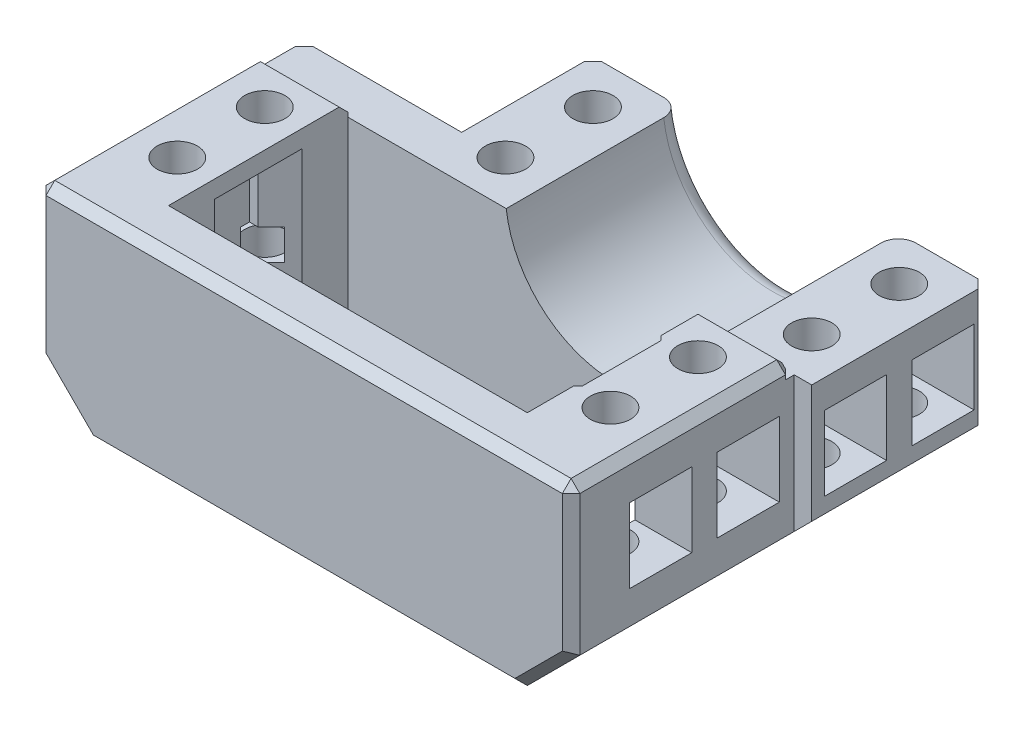
SolidWorks part; units mm, degrees
ref_plane "Front Plane" through (0, 0, 0) normal (0, 0, 1) x (1, 0, 0)
ref_plane "Top Plane" through (0, 0, 0) normal (0, 1, 0) x (1, 0, 0)
ref_plane "Right Plane" through (0, 0, 0) normal (1, 0, 0) x (0, 0, -1)
sketch "Sketch1" plane through (0, 0, 0) normal (0, 1, 0) x (1, 0, 0)
  line L0 (0, -10.25) -> (0, 10.25) construction
  line L1 (-20.5, 0) -> (20.5, 0) construction
  line L2 (-20.5, 10.25) -> (20.5, 10.25)
  line L3 (20.5, 10.25) -> (20.5, -10.25)
  line L4 (20.5, -10.25) -> (-20.5, -10.25)
  line L5 (-20.5, -10.25) -> (-20.5, 10.25)
  line L6 (0, -10.25) -> (0, -15.25) construction
  line L7 (0, -15.25) -> (-30.5, -15.25)
  line L8 (0, -15.25) -> (30.5, -15.25)
  line L9 (-30.5, -15.25) -> (-30.5, 30.25)
  line L10 (-30.5, 30.25) -> (30.5, 30.25)
  line L11 (30.5, 30.25) -> (30.5, -15.25)
  point P4 (0, 0)
  point P8 (0, 0)
  point P11 (0, 10.25)
  dimension "D1" = 41
  dimension "D2" = 20.5
  dimension "D3" = 5
  dimension "D4" = 30.5
  dimension "D5" = 30.5
  dimension "D6" = 45.5
extrude "Boss-Extrude1" add sketch "Sketch1" along normal blind 23
ref_plane "Plane1" through (0, 0, -30.25) normal (0, 0, -1) x (-1, 0, 0)
sketch "Sketch2" plane through (0, 0, -30.25) normal (0, 0, -1) x (-1, 0, 0)
  line L0 (0, 0) -> (0, 23) construction
  line L1 (-30.5, 0) -> (30.5, 0) construction
  line L2 (-30.5, 23) -> (30.5, 23) construction
  line L3 (0, 23) -> (-10, 23) construction
  circle A0 centre (-10, 23) radius 12.5
  dimension "D1" = 25
  dimension "D2" = 10
extrude "Cut-Extrude1" cut sketch "Sketch2" against normal blind 20
ref_plane "Plane2" through (30.5, 0, 0) normal (1, 0, 0) x (0, 0, -1)
sketch "Sketch3" plane through (30.5, 0, 0) normal (1, 0, 0) x (0, 0, -1)
  line L0 (30.25, 23) -> (10.25, 23)
  line L1 (10.25, 23) -> (10.25, 0)
  line L2 (10.25, 0) -> (30.25, 0)
  line L3 (30.25, 0) -> (30.25, 23)
extrude "Boss-Extrude2" add sketch "Sketch3" along normal blind 2
ref_plane "Plane3" through (0, 23, 0) normal (0, 1, 0) x (1, 0, 0)
sketch "Sketch4" plane through (0, 23, 0) normal (0, 1, 0) x (1, 0, 0)
  line L0 (-2.5, 20.25) -> (-7.5, 20.25) construction
  line L1 (-2.5, 10.25) -> (-2.5, 30.25) construction
  line L2 (-7.5, 15.25) -> (-7.5, 25.25) construction
  line L3 (22.5, 20.25) -> (27.5, 20.25) construction
  line L4 (22.5, 30.25) -> (22.5, 10.25) construction
  line L5 (27.5, 15.25) -> (27.5, 25.25) construction
  circle A0 centre (-7.5, 25.25) radius 2.3
  circle A1 centre (-7.5, 15.25) radius 2.3
  circle A2 centre (27.5, 25.25) radius 2.3
  circle A3 centre (27.5, 15.25) radius 2.3
  point P7 (-7.5, 20.25)
  point P14 (27.5, 20.25)
  dimension "D4" = 4.6
  dimension "D5" = 4.6
  dimension "D6" = 4.6
  dimension "D7" = 4.6
  dimension "D1" = 10
  dimension "D2" = 5
  dimension "D3" = 10
extrude "Cut-Extrude2" cut sketch "Sketch4" against normal up to next
sketch "Sketch5" plane through (0, 23, 0) normal (0, 1, 0) x (1, 0, 0)
  line L0 (0, 0) -> (20.5, 0) construction
  line L1 (20.5, -10.25) -> (20.5, 10.25) construction
  line L2 (20.5, -5) -> (20.5, 5) construction
  line L3 (20.5, 5) -> (24.75, 5) construction
  line L4 (20.5, -5) -> (24.75, -5) construction
  circle A0 centre (24.75, 5) radius 2.3
  circle A1 centre (24.75, -5) radius 2.3
  point P8 (20.5, 0)
  dimension "D1" = 4.6
  dimension "D2" = 4.6
extrude "Cut-Extrude3" cut sketch "Sketch5" against normal up to next
mirror "Mirror1" about plane through (0, 0, 0) normal (1, 0, 0) of "Cut-Extrude3"
sketch "Sketch6" plane through (0, 0, -30.25) normal (0, 0, -1) x (-1, 0, 0)
  line L0 (2.5, 23) -> (12.5, 23) construction
  line L1 (2.5, 23) -> (30.5, 23) construction
  line L2 (12.5, 23) -> (12.5, 19)
  line L3 (12.5, 19) -> (12.5, 14) construction
  line L4 (12.5, 14) -> (12.5, 9) construction
  line L5 (12.5, 9) -> (12.5, 4) construction
  line L6 (12.5, 4) -> (12.5, 0)
  line L7 (-32.5, 0) -> (30.5, 0) construction
  line L9 (30.5, 23) -> (30.5, 0) construction
  line L10 (30.5, 19) -> (30.5, 23)
  line L11 (30.5, 23) -> (12.5, 23)
  line L16 (30.5, 4) -> (30.5, 0)
  line L17 (30.5, 0) -> (12.5, 0)
  line L18 (12.5, 19) -> (12.5, 4)
  line L19 (30.5, 19) -> (30.5, 4)
  dimension "D1" = 10
  dimension "D2" = 4
  dimension "D3" = 5
  dimension "D4" = 5
  dimension "D5" = 5
extrude "Cut-Extrude4" cut sketch "Sketch6" against normal blind 15
ref_plane "Plane4" through (-12.5, 0, 0) normal (-1, 0, 0) x (0, 0, 1)
sketch "Sketch7" plane through (-12.5, 0, 0) normal (-1, 0, 0) x (0, 0, 1)
  line L0 (-30.25, 23) -> (-30.25, 13.25) construction
  line L2 (-30.25, 13.25) -> (-30.25, 9.75) construction
  line L3 (-30.25, 9.75) -> (-30.25, 0) construction
  line L4 (-30.25, 13.25) -> (-28.8, 13.25) construction
  line L5 (-28.8, 13.25) -> (-28.8, 9.75)
  line L6 (-28.8, 9.75) -> (-21.7, 9.75)
  line L7 (-21.7, 9.75) -> (-21.7, 13.25)
  line L8 (-21.7, 13.25) -> (-28.8, 13.25)
  line L9 (-21.7, 13.25) -> (-18.8, 13.25) construction
  line L10 (-18.8, 13.25) -> (-18.8, 9.75)
  line L11 (-18.8, 9.75) -> (-11.7, 9.75)
  line L12 (-11.7, 9.75) -> (-11.7, 13.25)
  line L13 (-11.7, 13.25) -> (-18.8, 13.25)
  dimension "D1" = 3.5
  dimension "D2" = 9.75
  dimension "D3" = 1.45
  dimension "D4" = 7.1
  dimension "D5" = 2.9
  dimension "D6" = 7.1
extrude "Cut-Extrude5" cut sketch "Sketch7" against normal blind 9 and the other way through all
fillet "Fillet1" radius 2 1 edges at (10, 10.5, -30.25)
ref_plane "Plane5" through (10, 0, 0) normal (-1, 0, 0) x (0, 0, 1)
mirror "Mirror2" about plane through (10, 0, 0) normal (-1, 0, 0) of "Cut-Extrude5"
sketch "Sketch8" plane through (30.5, 0, 0) normal (1, 0, 0) x (0, 0, -1)
  line L0 (0, 0) -> (0, 11.5) construction
  line L1 (-1.45, 11.5) -> (1.45, 11.5) construction
  line L2 (-1.45, 9.75) -> (-1.45, 13.25)
  line L3 (-1.45, 13.25) -> (-8.55, 13.25)
  line L4 (-8.55, 13.25) -> (-8.55, 9.75)
  line L5 (-8.55, 9.75) -> (-1.45, 9.75)
  line L6 (1.45, 9.75) -> (1.45, 13.25)
  line L7 (1.45, 13.25) -> (8.55, 13.25)
  line L8 (8.55, 13.25) -> (8.55, 9.75)
  line L9 (8.55, 9.75) -> (1.45, 9.75)
  point P6 (0, 11.5)
  point P9 (-1.45, 11.5)
  point P14 (1.45, 11.5)
  dimension "D1" = 2.9
  dimension "D2" = 3.5
  dimension "D3" = 7.1
  dimension "D4" = 7.1
extrude "Cut-Extrude6" cut sketch "Sketch8" against normal blind 9
mirror "Mirror3" about plane through (0, 0, 0) normal (1, 0, 0) of "Cut-Extrude6"
chamfer "Chamfer2" distance 5 8 edges at (-30.5, 13.25, 5) (-30.5, 13.25, -5) (-12.5, 13.25, -17.025) (-12.5, 13.25, -25.25) (32.5, 13.25, -25.25) (32.5, 13.25, -15.25) (30.5, 13.25, -5) (30.5, 13.25, 5)
chamfer "Chamfer3" distance 8 1 edges at (32.5, 0, -20.25)
chamfer "Chamfer4" distance 5 1 edges at (-12.5, 0, -22.75)
chamfer "Chamfer5" distance 1 5 edges at (32.5, 15.5, -30.25) (28.5, 4, -30.25) (8.5, 0, -30.25) (-10, 2.5, -30.25) (-12.5, 14, -30.25)
chamfer "Chamfer6" distance 6 1 edges at (-30.5, 0, 0)
chamfer "Chamfer7" distance 1 14 edges at (-17.15, 0, -15.25) (-27.5, 3, -15.25) (-30.5, 7.875, -15.25) (-21.5, 9.75, -15.25) (0, 23, 15.25) (30.5, 23, 2.5) (30.5, 14.5, 15.25) (27.5, 3, 15.25) (0, 0, 15.25) (-27.5, 3, 15.25) (-30.5, 14.5, 15.25) (-30.5, 23, 0) (-30.5, 18.125, -15.25) (-20.15, 13.25, -15.25)
ref_plane "Plane6" through (0, 33, 0) normal (0, 1, 0) x (1, 0, 0)
sketch "Sketch9" plane through (0, 33, 0) normal (0, 1, 0) x (1, 0, 0)
  line L0 (32.5, 10.25) -> (32.5, 30.25)
  line L1 (32.5, 30.25) -> (-31.9064, 30.25)
  line L2 (-31.9064, 30.25) -> (-31.9064, 10.25)
  line L3 (-31.9064, 10.25) -> (32.5, 10.25)
extrude "Cut-Extrude7" cut sketch "Sketch9" against normal blind 1.5 from surface starting at face at (-24.75, 23, -2.7)
chamfer "Chamfer8" distance 1 6 edges at (30.5, 21.75, -10.25) (30, 22.5, -10.25) (25, 23, -10.25) (-25, 23, -10.25) (-30, 22.5, -10.25) (-30.5, 21.75, -10.25)
sketch "Sketch10" plane through (0, 33, 0) normal (0, 1, 0) x (1, 0, 0)
  line L0 (-20.5, 10.25) -> (-20.5, 0) construction
  line L1 (-20.5, 9.25) -> (-20.5, -10.25) construction
  line L3 (-20.5, 2.5) -> (-24, 2.5)
  line L4 (-24, 2.5) -> (-24, -2.5)
  line L5 (-24, -2.5) -> (-20.5, -2.5)
  line L7 (-20.5, 2.5) -> (-20.5, 0)
  line L8 (-20.5, 0) -> (-20.5, -2.5)
  point P8 (-20.5, 0.9196)
  dimension "D1" = 2.5
  dimension "D2" = 5
  dimension "D3" = 3.5
  dimension "D4" = 10.25
extrude "Cut-Extrude8" cut sketch "Sketch10" against normal up to next from offset 12 offset against normal yes
chamfer "Chamfer9" distance 2.5 2 edges at (-20.5, 10.5, 2.5) (-20.5, 10.5, -2.5)
mirror "Mirror4" about plane through (0, 0, 0) normal (1, 0, 0) of "Cut-Extrude8"
chamfer "Chamfer10" distance 2.5 3 edges at (20.5, 10.5, -2.5) (20.5, 21, 0) (20.5, 10.5, 2.5)
